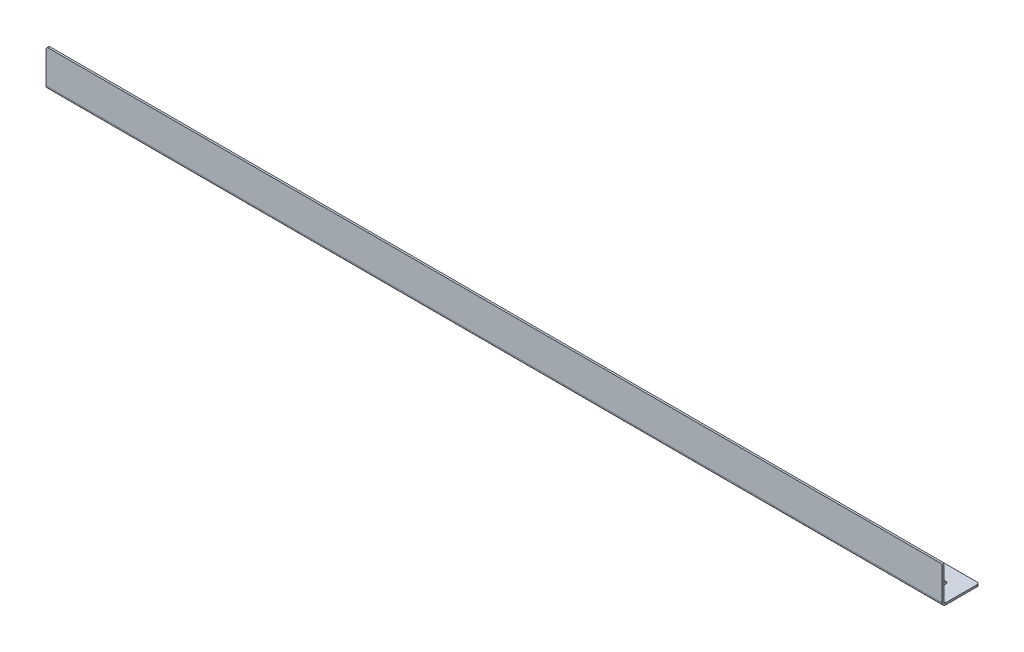
SolidWorks part; units mm, degrees
note: The reader was unsure of these and kept them because the rebuilt part matched: flange length of "Edge-Flange1".
material "5052-H36"
ref_plane "Front Plane" through (0, 0, 0) normal (0, 0, 1) x (1, 0, 0)
ref_plane "Top Plane" through (0, 0, 0) normal (0, 1, 0) x (1, 0, 0)
ref_plane "Right Plane" through (0, 0, 0) normal (1, 0, 0) x (0, 0, -1)
sketch "Sketch2" plane through (0, 0, 0) normal (0, 1, 0) x (1, 0, 0)
  line L1 (0, 0) -> (1219.2, 0)
  line L2 (0, 0) -> (0, 9.525)
  line L3 (-19.05, 50.8) -> (1219.2, 50.8)
  line L4 (1219.2, 0) -> (1219.2, 50.8)
  line L5 (-19.05, 50.8) -> (-19.05, 19.05)
  line L6 (-19.05, 19.05) -> (0, 9.525)
  dimension "D1" = 1219.2
  dimension "D2" = 1238.25
  dimension "D3" = 9.525
  dimension "D4" = 50.8
  dimension "D5" = 31.75
base flange "Base-Flange1" sketch "Sketch2" thickness 2.5908 reverse thickness direction no parameters "D1"=2.54
edge flange "Edge-Flange1" sketch "Sketch9" flange angle 90 flange length 50.8 bend radius 2.54 thickness 2.5908 relief rectangular parameters "D6"=10
sketch "Sketch9" plane through (0, 0, 0) normal (0, 0, -1) x (-1, 0, 0)
  line L2 (-1219.2, 0) -> (-1219.2, 48.2092)
  line L3 (-1219.2, 48.2092) -> (0, 48.2092)
  line L4 (0, 48.2092) -> (0, 0)
  line L5 (0, 0) -> (-1219.2, 0) construction
  line L6 (0, 0) -> (-1219.2, 0)
bend "EdgeBend1" bend radius 2.54 bend angle 90 parameters "D5"=1
hole_wizard "17/64 (0.26563) Diameter Hole1" positions "Sketch10" profile "Sketch11" hole size "17/64" standard "ANSI Inch" end condition through all
sketch "Sketch10" plane through (0, 0, 0) normal (0, 1, 0) x (1, 0, 0)
  line L1 (1219.2, 5.1308) -> (1219.2, 50.8) construction
  line L2 (0, 0) -> (1219.2, 0) construction
  point P0 (1193.8, 27.305)
  dimension "D2" = 25.4
  dimension "D3" = 27.305
sketch "Sketch11" plane through (1193.8, 0, -27.305) normal (1, 0, 0) x (0, 0, 1)
  line L0 (0, 0) -> (0, 2.5908)
  line L1 (0, 2.5908) -> (3.3735, 2.5908)
  line L2 (3.3735, 2.5908) -> (3.3735, 0)
  line L5 (3.3735, 0) -> (0, 0)
  line L11 (0, -6.35) -> (0, 107.95) construction
  dimension "Thru Hole Dia." = 6.747
  dimension "Thru Hole Depth" = 2.5908
fillet "Fillet1" radius 3.175 6 edges at (1219.2, 48.2092, -1.2954) (1219.2, -1.2954, -50.8) (0, 48.2092, -1.2954) (-19.05, -1.2954, -50.8) (-19.05, -1.2954, -19.05) (0, -1.2954, -9.525)
hole_wizard "17/64 (0.26563) Diameter Hole2" positions "Sketch13" profile "Sketch14" hole size "17/64" standard "ANSI Inch" end condition through all
sketch "Sketch13" plane through (0, 0, 0) normal (0, 1, 0) x (1, 0, 0)
  line L1 (-19.05, 47.625) -> (-19.05, 21.0123) construction
  line L2 (3.175, 0) -> (1216.025, 0) construction
  point P0 (3.81, 33.3375)
  dimension "D1" = 33.3375
  dimension "D2" = 22.86
sketch "Sketch14" plane through (3.81, 0, -33.3375) normal (1, 0, 0) x (0, 0, 1)
  line L0 (0, 0) -> (0, 2.5908)
  line L1 (0, 2.5908) -> (3.3735, 2.5908)
  line L2 (3.3735, 2.5908) -> (3.3735, 0)
  line L5 (3.3735, 0) -> (0, 0)
  line L11 (0, -6.35) -> (0, 107.95) construction
  dimension "Thru Hole Dia." = 6.747
  dimension "Thru Hole Depth" = 2.5908
hole_wizard "17/64 (0.26563) Diameter Hole3" positions "Sketch15" profile "Sketch16" hole size "17/64" standard "ANSI Inch" end condition through all
sketch "Sketch15" plane through (0, -2.5908, 0) normal (0, -1, 0) x (-1, 0, 0)
  line L0 (-1216.025, 50.8) -> (15.875, 50.8) construction
  line L1 (19.05, 47.625) -> (19.05, 21.0123) construction
  point P0 (-103.6574, 33.655)
  point P2 (-1102.8934, 33.655)
  point P9 (0, 0)
  dimension "D1" = 17.145
  dimension "D2" = 122.7074
  dimension "D3" = 999.236
sketch "Sketch16" plane through (103.6574, -2.5908, -33.655) normal (1, 0, 0) x (0, 0, -1)
  line L0 (0, 0) -> (0, 50.8)
  line L1 (0, 50.8) -> (3.3735, 50.8)
  line L2 (3.3735, 50.8) -> (3.3735, 0)
  line L5 (3.3735, 0) -> (0, 0)
  line L11 (0, -6.35) -> (0, 107.95) construction
  dimension "Thru Hole Dia." = 6.747
  dimension "Thru Hole Depth" = 50.8
sketch "Bend-Lines1" [suppressed] plane through (0, 0, 0) normal (0, 1, 0) x (1, 0, 0)
sketch "Bounding-Box1" [suppressed] plane through (0, 0, 0) normal (0, 1, 0) x (1, 0, 0)
sheet metal parameters "Sheet-Metal1" thickness 2.5908 parameters "D1"=2.54
flat pattern "Flat-Pattern1" [suppressed]
sketch "Bend-Lines2" plane through (0, 0, 0) normal (0, 1, 0) x (1, 0, 0)
sketch3d "Bounding-Box2" [suppressed]
  line L0 (1524, 50.8, 0) -> (-19.05, 50.8, 0) construction
  line L1 (1524, 0, 0) -> (-19.05, 0, 0) construction
  line L2 (1524, 50.8, 0) -> (1524, 0, 0) construction
  line L3 (-19.05, 50.8, 0) -> (-19.05, 0, 0) construction
sheet metal parameters "Sheet-Metal2" thickness 2.5908 parameters "D1"=2.54
flat pattern "Flat-Pattern1"
sketch "Bend-Lines2" plane through (0, 0, 0) normal (0, 1, 0) x (1, 0, 0)
  line L0 (0, 2.1185) -> (1524, 2.1185) construction
  line L1 (0, 2.1185) -> (1524, 2.1185) construction
sketch3d "Bounding-Box2" [suppressed]
  line L0 (1524, 50.8, 0) -> (0, 50.8, 0) construction
  line L1 (1524, -46.563, 0) -> (0, -46.563, 0) construction
  line L2 (1524, 50.8, 0) -> (1524, -46.563, 0) construction
  line L3 (0, 50.8, 0) -> (0, -46.563, 0) construction
bend of the flat pattern "Flatten-<EdgeBend1>1"
sheet metal parameters "Sheet-Metal3" thickness 2.5908 parameters "D1"=2.54
flat pattern "Flat-Pattern1"
sketch "Bend-Lines2" plane through (0, 0, 0) normal (0, 1, 0) x (1, 0, 0)
  line L0 (0, 2.1185) -> (1524, 2.1185) construction
  line L1 (0, 2.1185) -> (1524, 2.1185) construction
sketch3d "Bounding-Box2" [suppressed]
  line L0 (1524, 50.8, 0) -> (-19.05, 50.8, 0) construction
  line L1 (1524, -46.563, 0) -> (-19.05, -46.563, 0) construction
  line L2 (1524, 50.8, 0) -> (1524, -46.563, 0) construction
  line L3 (-19.05, 50.8, 0) -> (-19.05, -46.563, 0) construction
bend of the flat pattern "Flatten-<EdgeBend1>1"
sheet metal parameters "Sheet-Metal5" thickness 2.5908 parameters "D1"=2.54
flat pattern "Flat-Pattern1"
sketch "Bend-Lines2" plane through (0, 0, 0) normal (0, 1, 0) x (1, 0, 0)
  line L0 (0, 2.1185) -> (1219.2, 2.1185) construction
  line L1 (0, 2.1185) -> (1219.2, 2.1185) construction
sketch3d "Bounding-Box2" [suppressed]
  line L0 (1219.2, 50.8, 0) -> (-19.05, 50.8, 0) construction
  line L1 (1219.2, -46.563, 0) -> (-19.05, -46.563, 0) construction
  line L2 (1219.2, 50.8, 0) -> (1219.2, -46.563, 0) construction
  line L3 (-19.05, 50.8, 0) -> (-19.05, -46.563, 0) construction
bend of the flat pattern "Flatten-<EdgeBend1>1"
sheet metal parameters "Sheet-Metal6" thickness 2.5908 parameters "D1"=2.54
flat pattern "Flat-Pattern1"
sketch "Bend-Lines2" plane through (0, 0, 0) normal (0, 1, 0) x (1, 0, 0)
  line L0 (0, 2.1185) -> (1219.2, 2.1185) construction
  line L1 (0, 2.1185) -> (1219.2, 2.1185) construction
sketch3d "Bounding-Box2" [suppressed]
  line L0 (1219.2, 50.8, 0) -> (-19.05, 50.8, 0) construction
  line L1 (1219.2, -46.563, 0) -> (-19.05, -46.563, 0) construction
  line L2 (1219.2, 50.8, 0) -> (1219.2, -46.563, 0) construction
  line L3 (-19.05, 50.8, 0) -> (-19.05, -46.563, 0) construction
bend of the flat pattern "Flatten-<EdgeBend1>1"
